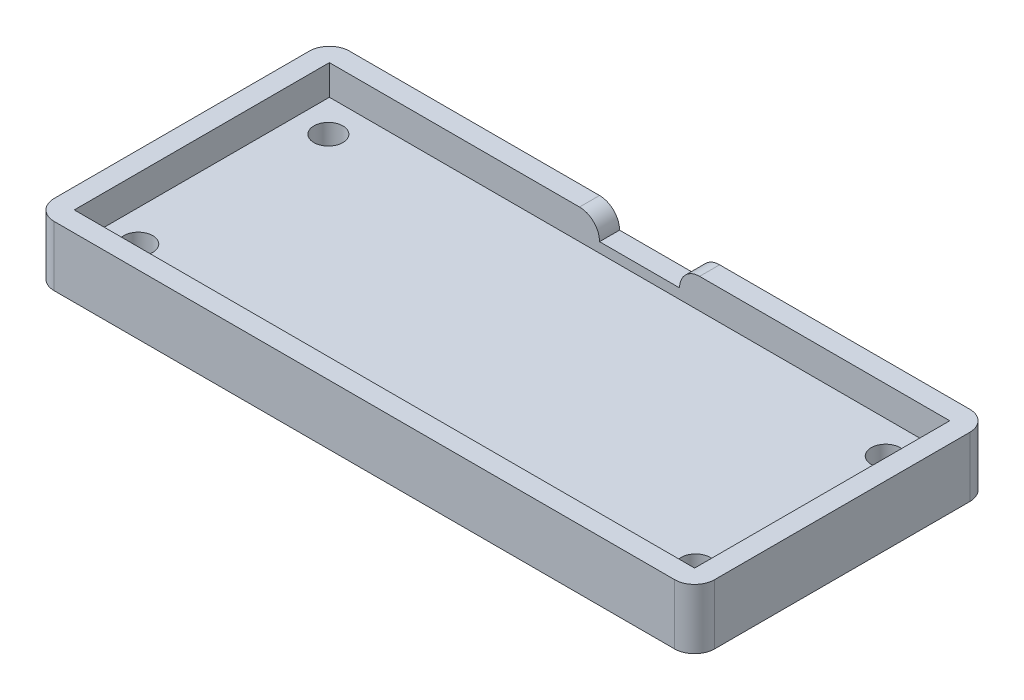
SolidWorks part; units mm, degrees
ref_plane "Front Plane" through (0, 0, 0) normal (0, 0, 1) x (1, 0, 0)
ref_plane "Top Plane" through (0, 0, 0) normal (0, 1, 0) x (1, 0, 0)
ref_plane "Right Plane" through (0, 0, 0) normal (1, 0, 0) x (0, 0, -1)
sketch "Sketch1" plane through (0, 0, 0) normal (0, 1, 0) x (1, 0, 0)
  line L0 (-5.15, 24.25) -> (60.85, 24.25)
  line L1 (0, 0) -> (55.7, 0) construction
  line L2 (0, 0) -> (0, 19) construction
  line L3 (0, 19) -> (55.7, 19) construction
  line L4 (55.7, 0) -> (55.7, 19) construction
  line L5 (27.85, 19) -> (27.85, 0) construction
  line L6 (0, 9.5) -> (55.7, 9.5) construction
  line L7 (-3.15, -3.25) -> (58.85, -3.25)
  line L8 (-3.15, -3.25) -> (-3.15, 22.25)
  line L9 (-3.15, 22.25) -> (58.85, 22.25)
  line L10 (58.85, -3.25) -> (58.85, 22.25)
  line L11 (27.85, 22.25) -> (27.85, -3.25) construction
  line L12 (-3.15, 9.5) -> (58.85, 9.5) construction
  line L13 (60.85, -5.25) -> (60.85, 24.25)
  line L14 (-5.15, -5.25) -> (60.85, -5.25)
  line L15 (-5.15, -5.25) -> (-5.15, 24.25)
  circle A0 centre (0, 19) radius 1.45
  circle A1 centre (55.7, 19) radius 1.45
  circle A2 centre (55.7, 0) radius 1.45
  circle A3 centre (0, 0) radius 1.45
  point P128 (27.85, 9.5)
  point P150 (27.85, 9.5)
  dimension "D6" = 2.9
  dimension "D1" = 55.7
  dimension "D2" = 19
  dimension "D3" = 62
  dimension "D4" = 25.5
  dimension "D5" = 2
extrude "Boss-Extrude1" add sketch "Sketch1" along normal blind 3 contours L7 L10 L9 L8 A1 A0 A2 A3 | L15 L14 L13 L0 L10 L7 L8 L9 region at (27.85, 0, -23.5271) region at (27.85, 0, -9.5)
extrude "Boss-Extrude3" add sketch "Sketch1<3>" along normal blind 6 contours L15 L14 L13 L0 L10 L7 L8 L9 region at (27.85, 0, -23.5271)
sketch "Sketch1<3>" plane through (0, 0, 0) normal (0, 1, 0) x (1, 0, 0) same geometry as "Sketch1"
fillet "Fillet1" radius 2 4 edges at (-5.15, 3, -24.25) (60.85, 3, -24.25) (60.85, 3, 5.25) (-5.15, 3, 5.25)
sketch "Sketch2" plane through (0, 6, 0) normal (0, 1, 0) x (1, 0, 0)
  line L0 (-3.15, 24.25) -> (58.85, 24.25) construction
  line L1 (23.85, 24.25) -> (31.85, 24.25)
  line L2 (23.85, 24.25) -> (23.85, 22.25)
  line L3 (23.85, 22.25) -> (31.85, 22.25)
  line L4 (31.85, 24.25) -> (31.85, 22.25)
  line L5 (27.85, 22.25) -> (27.85, 24.25) construction
  line L6 (23.85, 23.25) -> (31.85, 23.25) construction
  line L7 (-3.15, 22.25) -> (58.85, 22.25) construction
  point P8 (27.85, 22.25)
  point P176 (27.85, 23.25)
  dimension "D1" = 8
extrude "Cut-Extrude1" cut sketch "Sketch2" against normal blind 2
fillet "Fillet2" radius 2 2 edges at (31.85, 6, -23.25) (23.85, 6, -23.25)
